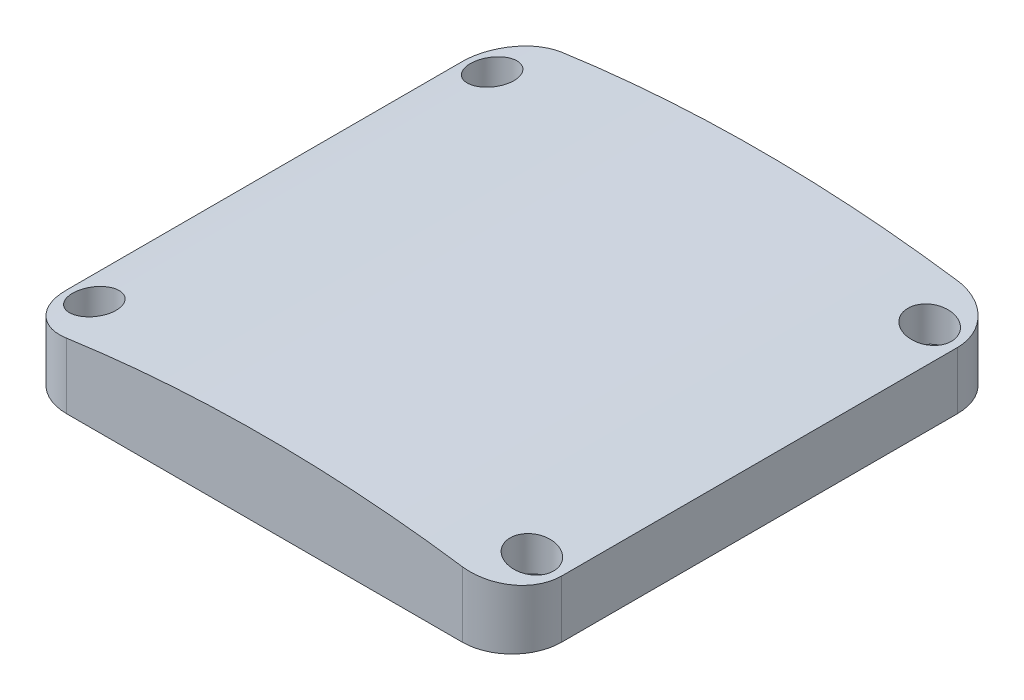
SolidWorks part; units mm, degrees
material "6061-T6 (SS)"
ref_plane "FWD" through (0, 0, 0) normal (0, 0, 1) x (1, 0, 0)
ref_plane "90-270" through (0, 0, 0) normal (0, 1, 0) x (1, 0, 0)
ref_plane "0-180" through (0, 0, 0) normal (1, 0, 0) x (0, 0, -1)
ref_axis "Axis1" through (0, 0, -215.99) along (0, 0, 1)
sketch "Sketch1" plane through (0, 0, 0) normal (0, 0, 1) x (1, 0, 0)
  line L0 (-31.623, 174.9652) -> (-31.623, 167.64)
  line L1 (-31.623, 167.64) -> (-24.003, 167.64)
  line L2 (24.003, 167.64) -> (-24.003, 167.64)
  line L5 (24.003, 167.64) -> (31.623, 167.64)
  line L6 (31.623, 167.64) -> (31.623, 174.9652)
  line L7 (0, 0) -> (0, 177.8) construction
  arc A0 (31.623, 174.9652) -> (-31.623, 174.9652) centre (0, 0) ccw
  point P9 (-27.813, 167.64)
  point P12 (27.813, 167.64)
  dimension "D1" = 177.8
  dimension "D2" = 63.246
  dimension "D3" = 10.16
  dimension "D4" = 7.62
  dimension "D5" = 167.64
  dimension "D6" = 7.3252
extrude "Boss-Extrude1" add sketch "Sketch1" along normal mid plane 63.246
fillet "Fillet1" radius 6.35 4 edges at (-31.623, 171.3026, -31.623) (31.623, 171.3026, -31.623) (31.623, 171.3026, 31.623) (-31.623, 171.3026, 31.623)
hole_wizard "#32 (0.116) Diameter Hole1" positions "Sketch6" profile "Sketch5" hole size "#32" standard "Ansi Inch"
sketch "Sketch6" plane through (0, 167.64, 0) normal (0, -1, 0) x (1, 0, 0)
  line L0 (0, 0) -> (0, -34.7083) construction
  point P1 (27.94, -25.4)
  point P3 (-27.94, -25.4)
  point P11 (27.94, 25.4)
  point P13 (-27.94, 25.4)
  dimension "D1" = 25.4
  dimension "D2" = 50.8
  dimension "D3" = 55.88
sketch "Sketch5" plane through (27.94, 167.64, -25.4) normal (1, 0, 0) x (0, 0, -1)
  line L0 (0, 0) -> (0, 3.81)
  line L1 (0, 3.81) -> (1.4732, 3.81)
  line L2 (1.4732, 3.81) -> (1.4732, 0)
  line L5 (1.4732, 0) -> (0, 0)
  line L10 (0, 3.81) -> (-1.4732, 3.81) construction
  line L11 (0, -6.35) -> (0, 107.95) construction
  dimension "Hole Dia." = 2.9464
  dimension "Hole Depth" = 3.81
  dimension "Drill Angle" = 180
sketch "Sketch7" plane through (0, 171.45, 0) normal (0, -1, 0) x (1, 0, 0)
  circle A0 centre (27.94, -25.4) radius 2.7813
  circle A1 centre (27.94, 25.4) radius 2.7813
  circle A2 centre (-27.94, 25.4) radius 2.7813
  circle A3 centre (-27.94, -25.4) radius 2.7813
  dimension "D1" = 5.5626
extrude "Cut-Extrude4" cut sketch "Sketch7" against normal through all
